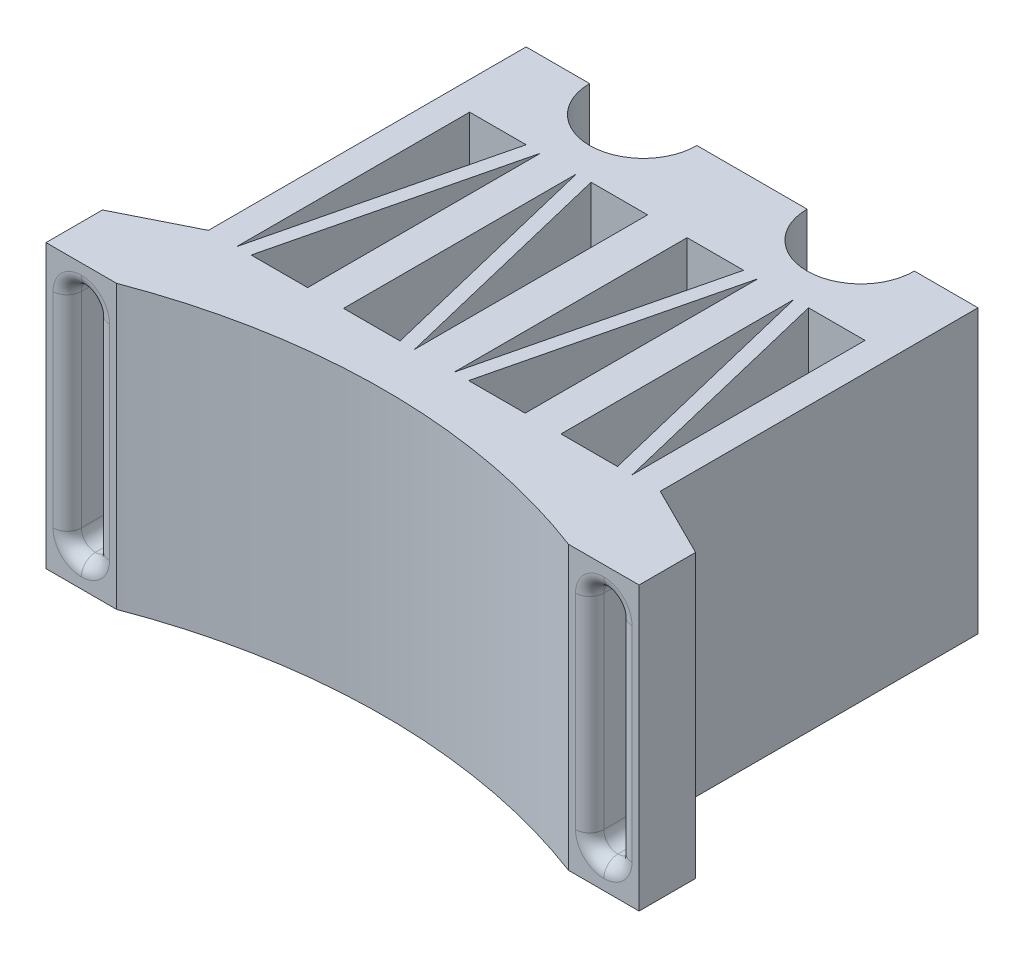
SolidWorks part; units mm, degrees
material "PLA"
ref_plane "Front Plane" through (0, 0, 0) normal (0, 0, 1) x (1, 0, 0)
ref_plane "Top Plane" through (0, 0, 0) normal (0, 1, 0) x (1, 0, 0)
ref_plane "Right Plane" through (0, 0, 0) normal (1, 0, 0) x (0, 0, -1)
sketch "Sketch1" plane through (0, 0, 0) normal (0, 1, 0) x (1, 0, 0)
  line L0 (40.64, -1000) -> (40.64, 49000) construction
  line L1 (0, 0) -> (81.28, 0)
  line L2 (0, 0) -> (0, 73.66)
  line L3 (0, 73.66) -> (81.28, 73.66)
  line L4 (81.28, 0) -> (81.28, 73.66)
  circle A0 centre (21.082, 73.66) radius 9.652
  circle A1 centre (60.198, 73.66) radius 9.652
  point P11 (40.64, 0)
  dimension "D3" = 19.304
  dimension "D1" = 81.28
  dimension "D2" = 73.66
  dimension "D4" = 39.116
extrude "Boss-Extrude1" add sketch "Sketch1" along normal blind 50.8 contours L1 L0 L3 A0 L2 | L0 L1 L4 L3 A1 region at (20.2808, 0, -35.1476) region at (60.9992, 0, -35.1476)
sketch "Sketch2" plane through (0, 0, 0) normal (0, 0, 1) x (1, 0, 0)
  line L0 (-6.35, 50.8) -> (-6.35, 0) construction
  line L1 (0, 50.8) -> (-12.7, 50.8)
  line L2 (0, 50.8) -> (0, 0)
  line L3 (0, 0) -> (-12.7, 0)
  line L4 (-12.7, 50.8) -> (-12.7, 0)
  line L5 (0, 0) -> (81.28, 0) construction
  line L6 (-8.89, 46.355) -> (-3.81, 46.355)
  line L7 (-8.89, 46.355) -> (-8.89, 4.445)
  line L8 (-8.89, 4.445) -> (-3.81, 4.445)
  line L9 (-3.81, 46.355) -> (-3.81, 4.445)
  line L10 (-8.89, 46.355) -> (-3.81, 4.445) construction
  line L11 (-8.89, 4.445) -> (-3.81, 46.355) construction
  point P7 (-6.35, 25.4)
  dimension "D1" = 12.7
  dimension "D2" = 5.08
  dimension "D3" = 41.91
extrude "Boss-Extrude2" add sketch "Sketch2" against normal blind 5.08
ref_plane "Plane1" through (40.64, 0, 0) normal (-1, 0, 0) x (0, 0, 1)
mirror "Mirror3" about plane through (40.64, 0, 0) normal (-1, 0, 0) of "Boss-Extrude2"
sketch "Sketch4" plane through (0, 50.8, 0) normal (0, 1, 0) x (1, 0, 0)
  line L0 (-12.7, 0) -> (93.98, 0) construction
  arc A0 (81.28, 0) -> (0, 0) centre (40.64, -106.8311) ccw
  dimension "D1" = 114.3
  dimension "D2" = 106.8311
  dimension "D3" = 40.64
extrude "Cut-Extrude1" cut sketch "Sketch4" against normal through all and the other way through all
sketch "Sketch5" plane through (0, 0, -73.66) normal (0, 0, -1) x (-1, 0, 0)
  line L1 (-40.64, 50.8) -> (-40.64, 0) construction
  line L2 (-30.734, 50.8) -> (-50.546, 50.8) construction
  line L3 (-30.734, 0) -> (-50.546, 0) construction
  line L4 (-50.546, 25.4) -> (-30.734, 25.4) construction
  line L5 (-50.546, 50.8) -> (-50.546, 0) construction
  line L6 (-30.734, 50.8) -> (-30.734, 0) construction
  circle A0 centre (-40.64, 41.91) radius 4.0132
  circle A1 centre (-40.64, 8.89) radius 4.0132
  circle A2 centre (-40.64, 25.4) radius 4.0132
  dimension "D1" = 8.0264
  dimension "D2" = 8.89
extrude "Cut-Extrude2" cut sketch "Sketch5" against normal blind 12.7
sketch "Sketch6" plane through (0, 0, 0) normal (0, -1, 0) x (1, 0, 0)
  line L7 (74.93, -40.64) -> (74.93, -11.43)
  line L8 (74.93, -11.43) -> (45.72, -11.43)
  line L9 (45.72, -11.43) -> (74.93, -40.64)
  line L10 (81.28, -5.08) -> (81.28, -73.66) construction
  line L11 (0, -73.66) -> (11.43, -73.66) construction
  line L12 (93.98, -5.08) -> (81.28, -5.08) construction
  line L13 (62.9739, -32.2761) -> (92.1839, -61.4861)
  line L14 (62.9739, -61.4861) -> (62.9739, -32.2761)
  line L15 (92.1839, -61.4861) -> (62.9739, -61.4861)
  line L16 (60.198, -35.56) -> (60.198, 49964.44) construction
  line L17 (28.2121, -61.4861) -> (57.4221, -61.4861)
  line L18 (57.4221, -61.4861) -> (57.4221, -32.2761)
  line L19 (57.4221, -32.2761) -> (28.2121, -61.4861)
  line L20 (74.676, -11.43) -> (45.466, -40.64)
  line L21 (45.466, -11.43) -> (74.676, -11.43)
  line L22 (45.466, -40.64) -> (45.466, -11.43)
  line L23 (40.64, -1035.56) -> (40.64, 48964.44) construction
  line L24 (30.734, -73.66) -> (50.546, -73.66) construction
  line L25 (0, -5.08) -> (0, -73.66) construction
  line L26 (35.814, -40.64) -> (35.814, -11.43)
  line L27 (35.814, -11.43) -> (6.604, -11.43)
  line L28 (6.604, -11.43) -> (35.814, -40.64)
  line L29 (23.8579, -32.2761) -> (53.0679, -61.4861)
  line L30 (23.8579, -61.4861) -> (23.8579, -32.2761)
  line L31 (53.0679, -61.4861) -> (23.8579, -61.4861)
  line L32 (-10.9039, -61.4861) -> (18.3061, -61.4861)
  line L33 (18.3061, -61.4861) -> (18.3061, -32.2761)
  line L34 (18.3061, -32.2761) -> (-10.9039, -61.4861)
  line L35 (35.56, -11.43) -> (6.35, -40.64)
  line L36 (6.35, -11.43) -> (35.56, -11.43)
  line L37 (6.35, -40.64) -> (6.35, -11.43)
  arc A1 (69.85, -73.66) -> (50.546, -73.66) centre (60.198, -73.66) ccw construction
  point P18 (60.198, -64.008)
  point P30 (40.64, -73.66)
  dimension "D1" = 12.1739
  dimension "D2" = 2.54
  dimension "D3" = 6.35
  dimension "D4" = 18.3061
  dimension "D5" = 6.35
extrude "Cut-Extrude3" [suppressed] cut sketch "Sketch6" against normal through all
sketch "Sketch9" plane through (0, 0, 0) normal (0, -1, 0) x (-1, 0, 0)
  line L4 (12.7, 5.08) -> (12.7, 0) construction
  line L5 (0, 5.08) -> (12.7, 5.08)
  line L6 (0, 5.08) -> (0, 8.89)
  line L8 (12.7, 5.08) -> (12.7, 10.16)
  line L9 (12.7, 10.16) -> (0, 16.51)
  line L10 (0, 5.08) -> (0, 73.66) construction
  line L11 (0, 16.51) -> (0, 8.89)
  dimension "D1" = 3.81
  dimension "D2" = 7.62
  dimension "D3" = 5.08
extrude "Boss-Extrude3" add sketch "Sketch9" against normal up to surface (50.8 mm away) up to face at (40.64, 50.8, -32.1746)
sketch "Sketch10" plane through (0, 0, -5.08) normal (0, 0, 1) x (1, 0, 0)
  line L0 (-3.81, 46.355) -> (-8.89, 46.355) construction
  line L1 (-3.81, 4.445) -> (-3.81, 46.355) construction
  line L2 (-8.89, 46.355) -> (-8.89, 4.445) construction
  line L3 (-8.89, 4.445) -> (-3.81, 4.445) construction
  line L4 (-3.81, 46.355) -> (-8.89, 46.355)
  line L5 (-3.81, 4.445) -> (-3.81, 46.355)
  line L6 (-8.89, 46.355) -> (-8.89, 4.445)
  line L7 (-8.89, 4.445) -> (-3.81, 4.445)
sketch "Sketch7" plane through (0, 0, 0) normal (0, -1, 0) x (1, 0, 0)
  line L0 (5.08, -16.51) -> (5.08, -58.42)
  line L1 (5.08, -58.42) -> (15.24, -58.42)
  line L2 (15.24, -58.42) -> (5.08, -16.51)
  line L3 (5.5454, -13.0392) -> (17.0781, -60.6115) construction
  line L4 (0, -16.51) -> (0, -73.66) construction
  line L5 (0, -73.66) -> (11.43, -73.66) construction
  line L6 (7.6936, -16.51) -> (17.8536, -16.51)
  line L7 (17.8536, -16.51) -> (17.8536, -58.42)
  line L8 (17.8536, -58.42) -> (7.6936, -16.51)
  line L9 (40.64, -1073.0686) -> (40.64, 48926.9314) construction
  line L10 (73.5864, -16.51) -> (63.4264, -16.51)
  line L11 (63.4264, -16.51) -> (63.4264, -58.42)
  line L12 (63.4264, -58.42) -> (73.5864, -16.51)
  line L13 (66.04, -58.42) -> (76.2, -16.51)
  line L14 (76.2, -58.42) -> (66.04, -58.42)
  line L15 (76.2, -16.51) -> (76.2, -58.42)
  line L16 (40.64, 16.764) -> (40.64, -16.764) construction
  line L17 (21.082, -1064.008) -> (21.082, 48935.992) construction
  line L18 (36.6186, -13.0392) -> (25.0859, -60.6115) construction
  line L19 (24.3104, -58.42) -> (34.4704, -16.51)
  line L20 (24.3104, -16.51) -> (24.3104, -58.42)
  line L21 (34.4704, -16.51) -> (24.3104, -16.51)
  line L22 (26.924, -58.42) -> (37.084, -16.51)
  line L23 (37.084, -58.42) -> (26.924, -58.42)
  line L24 (37.084, -16.51) -> (37.084, -58.42)
  line L25 (60.198, -1064.008) -> (60.198, 48935.992) construction
  line L26 (44.196, -16.51) -> (44.196, -58.42)
  line L27 (44.196, -58.42) -> (54.356, -58.42)
  line L28 (54.356, -58.42) -> (44.196, -16.51)
  line L29 (56.9696, -58.42) -> (46.8096, -16.51)
  line L30 (56.9696, -16.51) -> (56.9696, -58.42)
  line L31 (46.8096, -16.51) -> (56.9696, -16.51)
  arc A0 (30.734, -73.66) -> (11.43, -73.66) centre (21.082, -73.66) ccw construction
  arc A1 (69.85, -73.66) -> (50.546, -73.66) centre (60.198, -73.66) ccw construction
  point P28 (21.082, -64.008)
  point P42 (60.198, -64.008)
  dimension "D1" = 10.16
  dimension "D2" = 41.91
  dimension "D3" = 1.27
  dimension "D4" = 5.08
  dimension "D5" = 15.24
  dimension "D6" = 1.27
extrude "Cut-Extrude4" cut sketch "Sketch7" against normal through all
extrude "Cut-Extrude5" cut sketch "Sketch10" against normal through all
fillet "Fillet1" radius 2.54 4 edges at (-3.81, 46.355, -7.3025) (-8.89, 46.355, -6.0325) (-8.89, 4.445, -6.0325) (-3.81, 4.445, -7.3025)
mirror "Mirror4" about plane through (40.64, 0, 0) normal (-1, 0, 0) of "Boss-Extrude3", "Cut-Extrude5"
fillet "Fillet2" radius 2.54 4 edges at (90.17, 46.355, -6.0325) (85.09, 46.355, -7.3025) (85.09, 4.445, -7.3025) (90.17, 4.445, -6.0325)
fillet "Fillet3" radius 2.54 12 edges at (-4.5539, 5.1889, 0) (-3.81, 25.4, 0) (-4.5539, 45.6111, 0) (-8.1461, 45.6111, 0) (-8.89, 25.4, 0) (-8.1461, 5.1889, 0) (90.17, 25.4, 0) (89.4261, 45.6111, 0) (85.8339, 45.6111, 0) (85.09, 25.4, 0) (85.8339, 5.1889, 0) (89.4261, 5.1889, 0)
